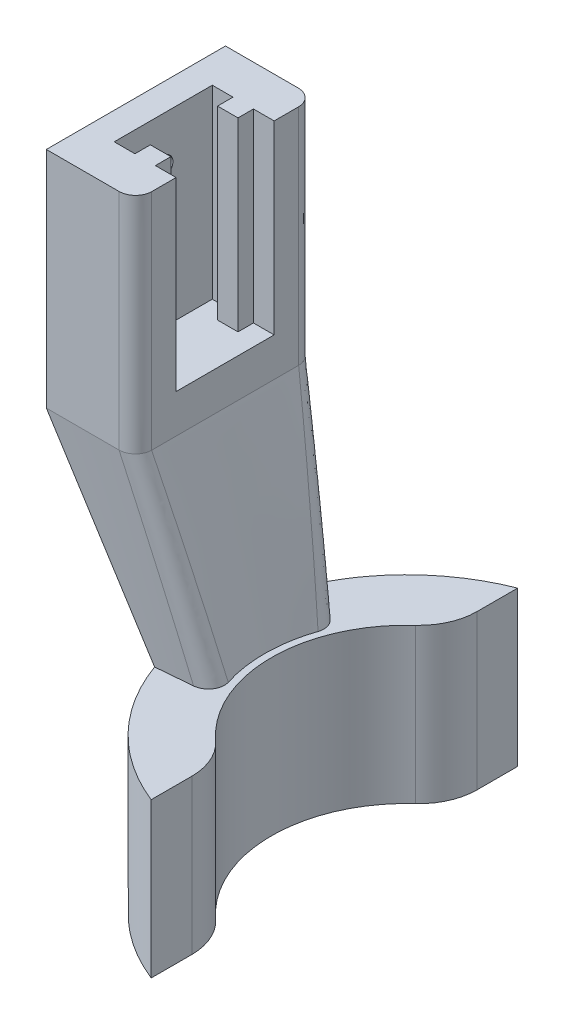
SolidWorks part; units mm, degrees
ref_plane "Front Plane" through (0, 0, 0) normal (0, 0, 1) x (1, 0, 0)
ref_plane "Top Plane" through (0, 0, 0) normal (0, 1, 0) x (1, 0, 0)
ref_plane "Right Plane" through (0, 0, 0) normal (1, 0, 0) x (0, 0, -1)
sketch "Sketch1" plane through (0, 0, 0) normal (0, 1, 0) x (1, 0, 0)
  line L3 (31.0345, 0) -> (-103.0514, 0) construction
  line L4 (-9.3416, 23.7273) -> (-9.3416, 14.7981)
  line L5 (-9.3416, -14.7981) -> (-9.3416, -23.7273)
  arc A0 (-9.3416, 14.7981) -> (-9.3416, -14.7981) centre (0, 0) ccw
  arc A1 (-9.3416, 23.7273) -> (-9.3416, -23.7273) centre (0, 0) ccw
  dimension "D1" = 17.5
  dimension "D2" = 25.5
extrude "Boss-Extrude1" add sketch "Sketch1" along normal blind 20
fillet "Fillet1" radius 7.5 2 edges at (-9.3416, 10, -14.7981) (-9.3416, 10, 14.7981)
sketch "Sketch2" plane through (0, 20, 0) normal (0, 1, 0) x (1, 0, 0)
  line L0 (-53.8431, 0) -> (13.3282, 0) construction
  line L1 (-23.995, 8.6307) -> (-16.2269, 8.6307)
  line L2 (-23.995, -8.6307) -> (-16.5494, -7.9948)
  arc A1 (-9.3416, 23.7273) -> (-9.3416, -23.7273) centre (0, 0) ccw construction
  arc A3 (-16.2269, 8.6307) -> (-16.5494, -7.9948) centre (0, 0) ccw
  arc A4 (-23.995, 8.6307) -> (-23.995, -8.6307) centre (0, 0) ccw
ref_plane "Plane1" through (0, 45, 0) normal (0, 1, 0) x (1, 0, 0)
sketch "Sketch3" plane through (0, 45, 0) normal (0, 1, 0) x (1, 0, 0)
  line L0 (8.2012, 0) -> (-25.5, 0) construction
  line L1 (-25.5, -24.3573) -> (-25.5, 19.0889) construction
  line L2 (-35.05, 11.6) -> (-23.5, 11.6)
  line L3 (-35.05, -11.6) -> (-23.5, -11.6)
  line L4 (-35.05, -11.6) -> (-35.05, 11.6)
  line L6 (-23.5, -11.6) -> (-23.5, 11.6)
  line L7 (-35.05, 0) -> (-53.8431, 0) construction
  arc A0 (-23.995, 8.6307) -> (-23.995, -8.6307) centre (0, 0) ccw construction
  dimension "D1" = 23.2
  dimension "D2" = 11.55
  dimension "D3" = 2
loft "Loft1" add profiles "Sketch2", "Sketch3"
fillet "Fillet2" radius 2 2 edges
sketch "Sketch5" plane through (0, 45, 0) normal (0, 1, 0) x (1, 0, 0)
  line L4 (-23.5, -9.512) -> (-23.5, 9.5251)
  line L5 (-25.6318, 11.6) -> (-35.05, 11.6)
  line L6 (-35.05, 11.6) -> (-35.05, -11.6)
  line L7 (-35.05, -11.6) -> (-25.6339, -11.6)
  line L8 (-23.5, -9.512) -> (-23.5, 9.5251)
  line L9 (-25.6318, 11.6) -> (-35.05, 11.6)
  line L10 (-35.05, 11.6) -> (-35.05, -11.6)
  line L11 (-35.05, -11.6) -> (-25.6339, -11.6)
  spline S2 degree 3 poles (-2969.3187, -556.4718) (-265.0696, -69.3473) (-19.7286, -8.1286) (-23.5711, 10.0678) (-23.6138, 10.2007) (-23.7239, 10.4526) (-23.791, 10.5718) (-23.9487, 10.7973) (-24.0394, 10.903) (-24.3354, 11.1875) (-24.5719, 11.3402) (-24.9522, 11.4939) (-25.0853, 11.5336) (-48.088, 16.0334) (-116.563, -351.7333) (-459.1202, -2956.4956) knots -16.742301 -16.742301 -16.742301 -16.742301 0.125 0.125 0.25 0.25 0.375 0.375 0.5 0.5 0.75 0.75 0.875 0.875 21.986911 21.986911 21.986911 21.986911 only from (-23.5, 9.5251) to (-25.6318, 11.6)
  spline S3 degree 3 poles (-589.7418, 2934.5196) (-106.4484, 233.9985) (-44.1121, -15.2784) (-25.0886, -11.5333) (-24.9548, -11.4934) (-24.6988, -11.3892) (-24.5772, -11.3255) (-24.3466, -11.1754) (-24.2369, -11.088) (-24.0392, -10.8968) (-23.9502, -10.7924) (-23.7922, -10.5658) (-23.724, -10.4438) (-18.1849, 2.2787) (-137.5439, 76.2126) (-1632.884, -2537.4929) knots -17.410609 -17.410609 -17.410609 -17.410609 0.125 0.125 0.25 0.25 0.375 0.375 0.5 0.5 0.625 0.625 0.75 0.75 13.27066 13.27066 13.27066 13.27066 only from (-25.6339, -11.6) to (-23.5, -9.512)
  spline S4 degree 3 poles (-23.5, 9.5251) (-23.5, 9.6639) (-23.5146, 9.8001) (-23.5711, 10.0678) (-23.6138, 10.2007) (-23.7239, 10.4526) (-23.791, 10.5718) (-23.9487, 10.7973) (-24.0394, 10.903) (-24.3354, 11.1875) (-24.5719, 11.3402) (-24.9522, 11.4939) (-25.0853, 11.5336) (-25.3561, 11.5866) (-25.4931, 11.6) (-25.6318, 11.6) knots 0 0 0 0 0.125 0.125 0.25 0.25 0.375 0.375 0.5 0.5 0.75 0.75 0.875 0.875 1 1 1 1
  spline S5 degree 3 poles (-25.6339, -11.6) (-25.4947, -11.6) (-25.3579, -11.5863) (-25.0886, -11.5333) (-24.9548, -11.4934) (-24.6988, -11.3892) (-24.5772, -11.3255) (-24.3466, -11.1754) (-24.2369, -11.088) (-24.0392, -10.8968) (-23.9502, -10.7924) (-23.7922, -10.5658) (-23.724, -10.4438) (-23.5597, -10.0665) (-23.5, -9.7906) (-23.5, -9.512) knots 0 0 0 0 0.125 0.125 0.25 0.25 0.375 0.375 0.5 0.5 0.625 0.625 0.75 0.75 1 1 1 1
  dimension "D1" = 0
extrude "Boss-Extrude2" add sketch "Sketch5" along normal blind 5
sketch "Sketch6" plane through (0, 50, 0) normal (0, 1, 0) x (1, 0, 0)
  line L0 (-26.18, -6.35) -> (-23.5, -6.35)
  line L1 (-31.51, -6.35) -> (-28.83, -6.35)
  line L2 (-31.51, -6.35) -> (-31.51, 6.35)
  line L3 (-31.51, 6.35) -> (-28.83, 6.35)
  line L4 (-23.5, -9.512) -> (-23.5, 9.5251)
  line L5 (-25.6318, 11.6) -> (-35.05, 11.6)
  line L6 (-35.05, 11.6) -> (-35.05, -11.6)
  line L7 (-35.05, -11.6) -> (-25.6339, -11.6)
  line L8 (-23.5, -9.512) -> (-23.5, 9.5251)
  line L9 (-25.6318, 11.6) -> (-35.05, 11.6)
  line L10 (-35.05, 11.6) -> (-35.05, -11.6)
  line L11 (-35.05, -11.6) -> (-25.6339, -11.6)
  line L12 (-23.5, -6.35) -> (-23.5, 6.35)
  line L14 (-28.83, -6.35) -> (-28.83, -4.35)
  line L16 (-26.18, -6.35) -> (-26.18, -4.35)
  line L18 (-28.83, 6.35) -> (-28.83, 4.35)
  line L20 (-26.18, 6.35) -> (-26.18, 4.35)
  line L21 (-26.18, 6.35) -> (-23.5, 6.35)
  line L22 (-28.83, 4.35) -> (-26.18, 4.35)
  line L23 (-28.83, -4.35) -> (-26.18, -4.35)
  spline S2 degree 3 poles (-589.7418, 2934.5196) (-106.4484, 233.9985) (-44.1121, -15.2784) (-25.0886, -11.5333) (-24.9548, -11.4934) (-24.6988, -11.3892) (-24.5772, -11.3255) (-24.3466, -11.1754) (-24.2369, -11.088) (-24.0392, -10.8968) (-23.9502, -10.7924) (-23.7922, -10.5658) (-23.724, -10.4438) (-18.1849, 2.2787) (-137.5439, 76.2126) (-1632.884, -2537.4929) knots -17.410609 -17.410609 -17.410609 -17.410609 0.125 0.125 0.25 0.25 0.375 0.375 0.5 0.5 0.625 0.625 0.75 0.75 13.27066 13.27066 13.27066 13.27066 only from (-25.6339, -11.6) to (-23.5, -9.512)
  spline S3 degree 3 poles (-2969.3187, -556.4718) (-265.0696, -69.3473) (-19.7286, -8.1286) (-23.5711, 10.0678) (-23.6138, 10.2007) (-23.7239, 10.4526) (-23.791, 10.5718) (-23.9487, 10.7973) (-24.0394, 10.903) (-24.3354, 11.1875) (-24.5719, 11.3402) (-24.9522, 11.4939) (-25.0853, 11.5336) (-48.088, 16.0334) (-116.563, -351.7333) (-459.1202, -2956.4956) knots -16.742301 -16.742301 -16.742301 -16.742301 0.125 0.125 0.25 0.25 0.375 0.375 0.5 0.5 0.75 0.75 0.875 0.875 21.986911 21.986911 21.986911 21.986911 only from (-23.5, 9.5251) to (-25.6318, 11.6)
  spline S4 degree 3 poles (-25.6339, -11.6) (-25.4947, -11.6) (-25.3579, -11.5863) (-25.0886, -11.5333) (-24.9548, -11.4934) (-24.6988, -11.3892) (-24.5772, -11.3255) (-24.3466, -11.1754) (-24.2369, -11.088) (-24.0392, -10.8968) (-23.9502, -10.7924) (-23.7922, -10.5658) (-23.724, -10.4438) (-23.5597, -10.0665) (-23.5, -9.7906) (-23.5, -9.512) knots 0 0 0 0 0.125 0.125 0.25 0.25 0.375 0.375 0.5 0.5 0.625 0.625 0.75 0.75 1 1 1 1
  spline S5 degree 3 poles (-23.5, 9.5251) (-23.5, 9.6639) (-23.5146, 9.8001) (-23.5711, 10.0678) (-23.6138, 10.2007) (-23.7239, 10.4526) (-23.791, 10.5718) (-23.9487, 10.7973) (-24.0394, 10.903) (-24.3354, 11.1875) (-24.5719, 11.3402) (-24.9522, 11.4939) (-25.0853, 11.5336) (-25.3561, 11.5866) (-25.4931, 11.6) (-25.6318, 11.6) knots 0 0 0 0 0.125 0.125 0.25 0.25 0.375 0.375 0.5 0.5 0.75 0.75 0.875 0.875 1 1 1 1
  dimension "D2" = 2.65
  dimension "D3" = 2.68
  dimension "D4" = 12.7
  dimension "D5" = 5.25
  dimension "D6" = 2.68
  dimension "D7" = 2.68
  dimension "D8" = 2
  dimension "D1" = 0
extrude "Boss-Extrude3" add sketch "Sketch6" along normal blind 24
sketch "Sketch7" plane through (-31.51, 0, 0) normal (1, 0, 0) x (0, 0, -1)
  line L0 (0, 134.8049) -> (0, 102.8956) construction
  line L1 (-6.35, 50) -> (6.35, 50) construction
  circle A0 centre (0, 68) radius 1.25
  circle A1 centre (0, 56) radius 1.25
  dimension "D1" = 2.5
  dimension "D2" = 12
  dimension "D3" = 6
extrude "Cut-Extrude1" cut sketch "Sketch7" against normal through all
